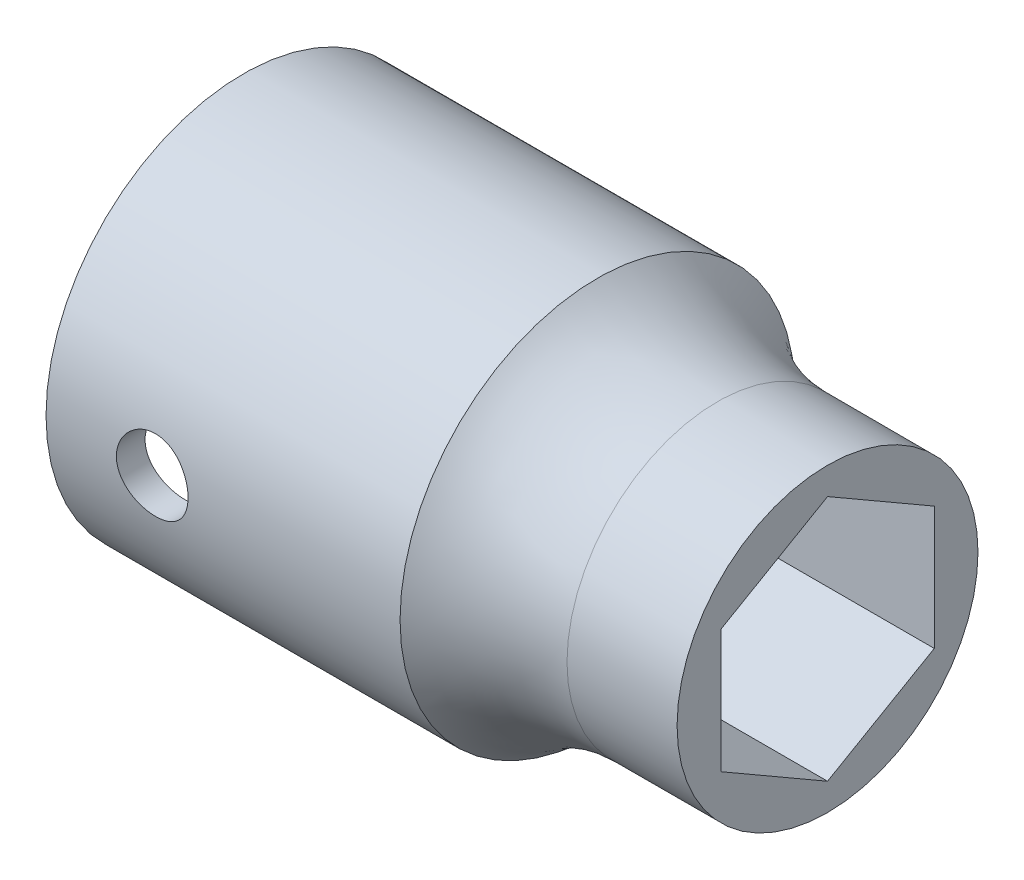
SolidWorks part; units mm, degrees
ref_plane "Alzado" through (0, 0, 0) normal (0, 0, 1) x (1, 0, 0)
ref_plane "Planta" through (0, 0, 0) normal (0, 1, 0) x (1, 0, 0)
ref_plane "Vista lateral" through (0, 0, 0) normal (1, 0, 0) x (0, 0, -1)
sketch "Croquis1" plane through (0, 0, 0) normal (1, 0, 0) x (0, 0, -1)
  line L1 (0, -6.9282) -> (6, -3.4641) construction
  line L2 (6, -3.4641) -> (6, 3.4641) construction
  line L3 (6, 3.4641) -> (0, 6.9282) construction
  line L4 (0, 6.9282) -> (-6, 3.4641) construction
  line L5 (-6, 3.4641) -> (-6, -3.4641) construction
  line L6 (-6, -3.4641) -> (0, -6.9282) construction
  circle A0 centre (0, 0) radius 6.4 construction
  circle A1 centre (0, 0) radius 6 construction
  circle A2 centre (0, 0) radius 8.5
  dimension "D2" = 12.8
  dimension "D3" = 17
  dimension "D1" = 12
extrude "Saliente-Extruir1" add sketch "Croquis1" along normal blind 30
sketch "Croquis2" plane through (30, 0, 0) normal (1, 0, 0) x (0, 0, -1)
  line L1 (0, -6.9628) -> (6.03, -3.4814)
  line L2 (6.03, -3.4814) -> (6.03, 3.4814)
  line L3 (6.03, 3.4814) -> (0, 6.9628)
  line L4 (0, 6.9628) -> (-6.03, 3.4814)
  line L5 (-6.03, 3.4814) -> (-6.03, -3.4814)
  line L6 (-6.03, -3.4814) -> (0, -6.9628)
  circle A0 centre (0, 0) radius 6.03 construction
  dimension "D1" = 12.06
extrude "Cortar-Extruir1" cut sketch "Croquis2" against normal blind 8.5
sketch "Croquis9" plane through (0, 0, 0) normal (-1, 0, 0) x (0, 0, 1)
  circle A0 centre (0, 0) radius 11.15
  dimension "D1" = 22.3
extrude "Saliente-Extruir5" add sketch "Croquis9" against normal blind 20
sketch "Croquis3" plane through (0, 0, 0) normal (-1, 0, 0) x (0, 0, 1)
  circle A0 centre (0, 0) radius 9.53
  dimension "D1" = 19.06
extrude "Cortar-Extruir2" cut sketch "Croquis3" against normal blind 19
sketch "Croquis4" plane through (19, 0, 0) normal (-1, 0, 0) x (0, 0, 1)
  circle A0 centre (0, 0) radius 2.035
  dimension "D1" = 4.07
extrude "Cortar-Extruir3" cut sketch "Croquis4" against normal up to next
sketch "Croquis5" plane through (0, 0, 0) normal (0, 0, 1) x (1, 0, 0)
  circle A0 centre (6, 0) radius 2.025
  dimension "D1" = 4.05
  dimension "D2" = 6
extrude "Cortar-Extruir4" cut sketch "Croquis5" against normal through all and the other way through all
sketch "Croquis7" plane through (30, 0, 0) normal (1, 0, 0) x (0, 0, -1)
  line L2 (-6.03, -3.4814) -> (0, -6.9628)
  line L8 (-6.03, -3.4814) -> (0, -6.9628)
  line L9 (6.03, 3.4814) -> (0, 6.9628)
  line L10 (0, -6.9628) -> (6.03, -3.4814)
  line L11 (0, -6.9628) -> (6.03, -3.4814)
  line L15 (6.03, 3.4814) -> (0, 6.9628)
  line L18 (6.03, -3.4814) -> (6.03, 3.4814)
  line L19 (6.03, -3.4814) -> (6.03, 3.4814)
  line L20 (0, 6.9628) -> (-6.03, 3.4814)
  line L21 (0, 6.9628) -> (-6.03, 3.4814)
  line L22 (-6.03, 3.4814) -> (-6.03, -3.4814)
  line L23 (-6.03, 3.4814) -> (-6.03, -3.4814)
  circle A0 centre (0, 0) radius 8.5 construction
  circle A1 centre (0, 0) radius 8.5
  dimension "D1" = 0
extrude "Saliente-Extruir3" add sketch "Croquis7" along normal blind 3
fillet "Redondeo1" radius 10 1 edges at (20, 0, 8.5)
equation "\"D1@Croquis2\" = 12 + \"tolerancia\""
equation "\"D1@Croquis3\"= 19 + \"tolerancia\""
equation "\"tolerancia\" = 0.06"
